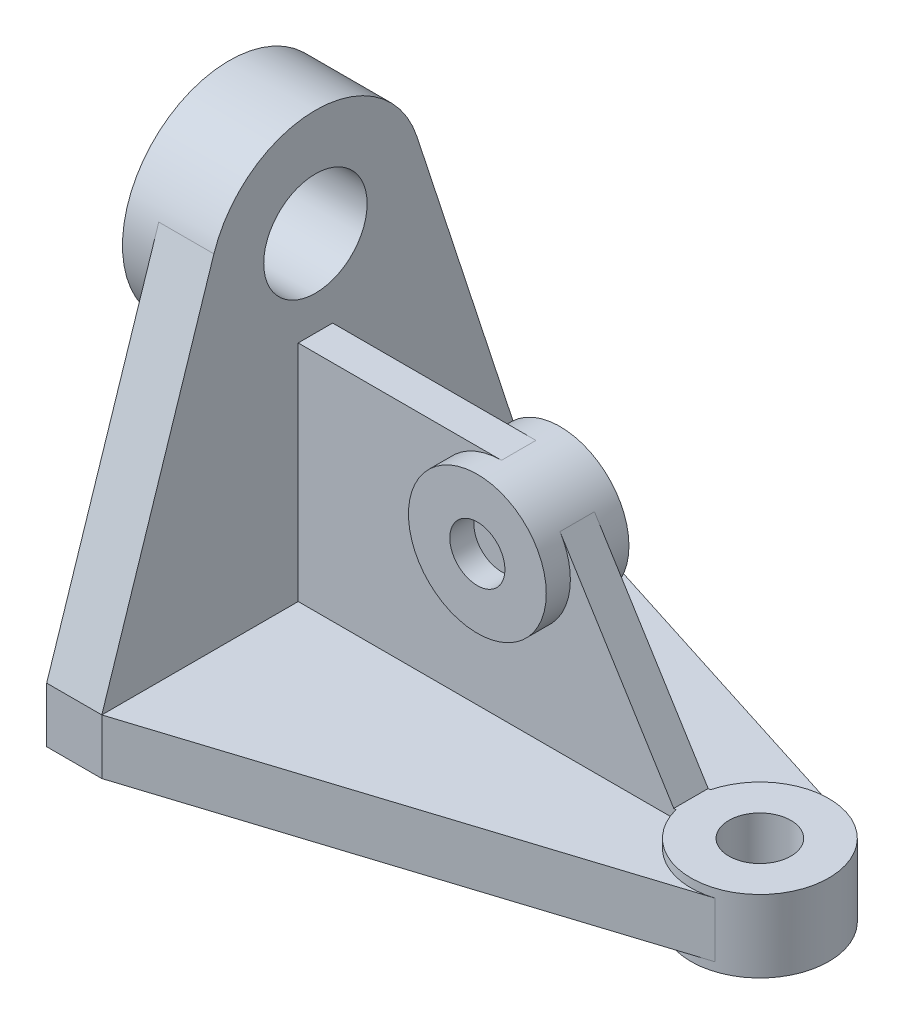
SolidWorks part; units mm, degrees
ref_plane "Front Plane" through (0, 0, 0) normal (0, 0, 1) x (1, 0, 0)
ref_plane "Top Plane" through (0, 0, 0) normal (0, 1, 0) x (1, 0, 0)
ref_plane "Right Plane" through (0, 0, 0) normal (1, 0, 0) x (0, 0, -1)
sketch "Sketch1" plane through (0, 0, 0) normal (0, 1, 0) x (1, 0, 0)
  line L0 (0, 62) -> (0, -62)
  line L1 (0, -62) -> (135.0598, -19.0599)
  line L2 (0, 0) -> (86.6402, 0) construction
  line L3 (0, 62) -> (135.0598, 19.0599)
  arc A0 (135.0598, -19.0599) -> (135.0598, 19.0599) centre (129, 0) ccw
  circle A1 centre (129, 0) radius 9
  dimension "D1" = 40
  dimension "D4" = 18
  dimension "D2" = 124
  dimension "D3" = 129
extrude "Boss-Extrude1" add sketch "Sketch1" along normal blind 16
sketch "Sketch2" plane through (0, 16, 0) normal (0, 1, 0) x (1, 0, 0)
  circle A0 centre (129, 0) radius 20
  arc A1 (135.0598, -19.0599) -> (135.0598, 19.0599) centre (129, 0) ccw construction
  circle A2 centre (129, 0) radius 9 construction
  circle A3 centre (129, 0) radius 9
extrude "Boss-Extrude2" add sketch "Sketch2" along normal blind 2.5 and the other way blind 18.5
sketch "Sketch3" plane through (0, 0, 0) normal (-1, 0, 0) x (0, 0, 1)
  line L0 (-62, 0) -> (62, 0)
  line L1 (62, 0) -> (62, 16)
  line L2 (62, 16) -> (29.4686, 115.6228)
  line L3 (-62, 0) -> (-62, 16)
  line L4 (-62, 16) -> (-29.4686, 115.6228)
  arc A0 (29.4686, 115.6228) -> (-29.4686, 115.6228) centre (0, 106) ccw
  circle A1 centre (0, 106) radius 15
  dimension "D1" = 62
  dimension "D3" = 30
  dimension "D2" = 106
extrude "Boss-Extrude3" add sketch "Sketch3" along normal blind 16
sketch "Sketch5" plane through (0, 0, 0) normal (1, 0, 0) x (0, 0, -1)
  circle A0 centre (0, 106) radius 15 construction
  circle A1 centre (0, 106) radius 15
  circle A2 centre (0, 106) radius 31
  arc A3 (29.4686, 115.6228) -> (-29.4686, 115.6228) centre (0, 106) ccw construction
extrude "Boss-Extrude4" add sketch "Sketch5" against normal blind 25
sketch "Sketch6" plane through (0, 0, 0) normal (0, 0, 1) x (1, 0, 0)
  line L0 (0, 16) -> (0, 115.6228) construction
  line L1 (0, 0) -> (135.0598, 0) construction
  circle A0 centre (59, 61) radius 20
  circle A1 centre (59, 61) radius 8
  dimension "D1" = 40
  dimension "D2" = 16
  dimension "D3" = 59
  dimension "D4" = 61
extrude "Boss-Extrude5" add sketch "Sketch6" along normal mid plane 24 separate body
sketch "Sketch7" plane through (0, 0, 0) normal (0, 0, 1) x (1, 0, 0)
  line L0 (149, 18.5) -> (109, 18.5) construction
  line L2 (0, 16) -> (135.0598, 16) construction
  line L3 (0, 16) -> (0, 115.6228) construction
  line L4 (111, 18.5) -> (109, 18.5)
  line L6 (0, 16) -> (111, 16)
  line L7 (0, 16) -> (0, 81)
  line L8 (59, 81) -> (0, 81)
  line L9 (75.9811, 71.566) -> (109, 18.5)
  line L10 (111, 18.5) -> (111, 16)
  line L11 (149, -2.5) -> (149, 18.5) construction
  circle A0 centre (59, 61) radius 20 construction
  arc A1 (75.9811, 71.566) -> (59, 81) centre (59, 61) ccw
  dimension "D1" = 38
extrude "Boss-Extrude6" add sketch "Sketch7" along normal mid plane 10
